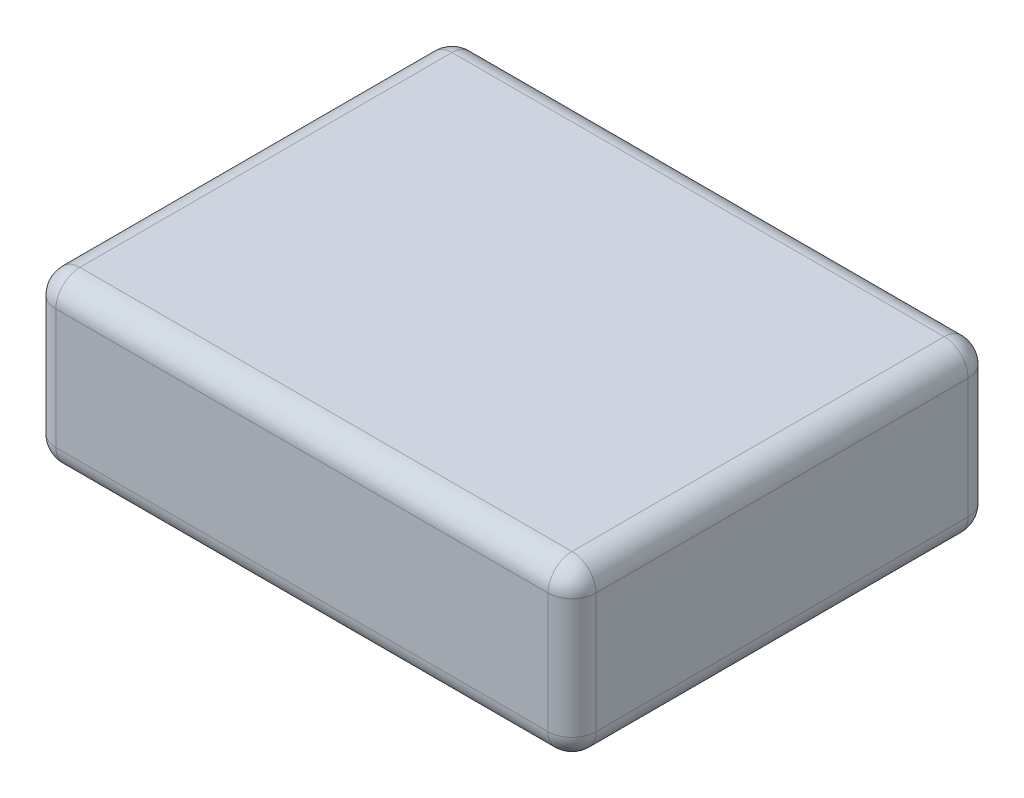
SolidWorks part; units mm, degrees
ref_plane "Front Plane" through (0, 0, 0) normal (0, 0, 1) x (1, 0, 0)
ref_plane "Top Plane" through (0, 0, 0) normal (0, 1, 0) x (1, 0, 0)
ref_plane "Right Plane" through (0, 0, 0) normal (1, 0, 0) x (0, 0, -1)
sketch "Sketch1" plane through (0, 0, 0) normal (0, 1, 0) x (1, 0, 0)
  line L1 (-45, -35) -> (45, -35)
  line L2 (-45, -35) -> (-45, 35)
  line L3 (-45, 35) -> (45, 35)
  line L4 (45, -35) -> (45, 35)
  line L5 (-45, -35) -> (45, 35) construction
  line L6 (-45, 35) -> (45, -35) construction
  point P0 (0, 0)
  dimension "D1" = 90
  dimension "D2" = 70
extrude "Boss-Extrude1" add sketch "Sketch1" along normal blind 28
fillet "Fillet1" radius 4 8 edges at (0, 0, -35) (-45, 0, 0) (0, 0, 35) (45, 0, 0) (0, 28, 35) (-45, 28, 0) (0, 28, -35) (45, 28, 0)
fillet "Fillet2" radius 4 12 edges at (-43.8284, 26.8284, 33.8284) (-43.8284, 1.1716, 33.8284) (-43.8284, 26.8284, -33.8284) (-43.8284, 1.1716, -33.8284) (43.8284, 26.8284, -33.8284) (43.8284, 1.1716, -33.8284) (43.8284, 26.8284, 33.8284) (43.8284, 1.1716, 33.8284) (-45, 14, 35) (-45, 14, -35) (45, 14, -35) (45, 14, 35)
